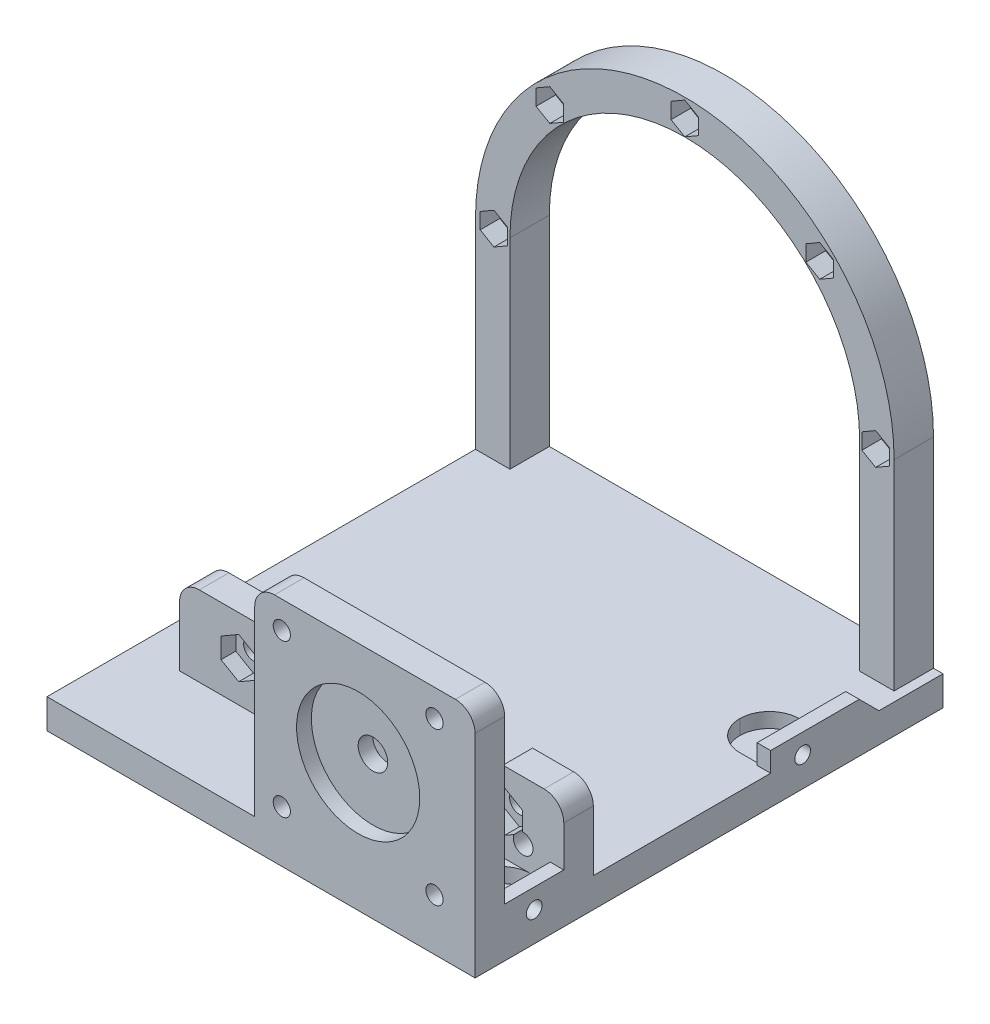
SolidWorks part; units mm, degrees
ref_plane "Front Plane" through (0, 0, 0) normal (0, 0, 1) x (1, 0, 0)
ref_plane "Top Plane" through (0, 0, 0) normal (0, 1, 0) x (1, 0, 0)
ref_plane "Right Plane" through (0, 0, 0) normal (1, 0, 0) x (0, 0, -1)
sketch "Sketch1" plane through (0, 0, 0) normal (0, 0, 1) x (1, 0, 0)
  circle A0 centre (0, 0) radius 3.5
  circle A1 centre (-13.7, 0) radius 2.25
  circle A2 centre (13.7, 0) radius 2.25
  circle A3 centre (0, 0) radius 18.5
  dimension "D3" = 4.5
  dimension "D4" = 7
  dimension "D5" = 37
  dimension "D1" = 13.7
  dimension "D2" = 13.7
extrude "Boss-Extrude1" add sketch "Sketch1" along normal blind 6
sketch "Sketch3" plane through (0, 0, 6) normal (0, 0, 1) x (1, 0, 0)
  line L0 (-18.5, 0) -> (-18.5, -46.68)
  line L1 (18.5, 0) -> (18.5, -46.68)
  line L2 (18.5, -46.68) -> (-18.5, -46.68)
  line L3 (15.5, 0) -> (15.5, -43.68)
  line L4 (15.5, -43.68) -> (-15.5, -43.68)
  line L5 (-15.5, 0) -> (-15.5, -43.68)
  line L6 (-15.5, -43.68) -> (0, -18.5) construction
  line L7 (0, -18.5) -> (15.5, -43.68) construction
  line L8 (-15.5, -40.8186) -> (-1.7125, -18.4206)
  line L9 (0, 0) -> (0, -18.5) construction
  line L10 (0, -18.5) -> (0, -43.68) construction
  line L11 (-13.7386, -43.68) -> (0, -21.3614)
  line L12 (15.5, -40.8186) -> (1.7125, -18.4206)
  line L13 (13.7386, -43.68) -> (0, -21.3614)
  line L14 (-15.5, -10.0995) -> (-18.5, 0)
  line L15 (18.5, 0) -> (15.5, -10.0995)
  line L16 (-3, -20.5121) -> (-3, -18.2551)
  line L17 (3, -20.5121) -> (3, -18.2551)
  circle A0 centre (0, 0) radius 18.5 construction
  circle A1 centre (0, 0) radius 18.5
  circle M4 centre (0, 0) radius 18.5
  dimension "D1" = 46.68
  dimension "D3" = 1.5
  dimension "D4" = 1.5
  dimension "D5" = 3
  dimension "D2" = 3
extrude "Boss-Extrude2" add sketch "Sketch3" against normal blind 6 contours L5 L0 L2 L1 L3 L4 M4 | L13 L4 L3 L12 L8 L5 L11 M4 | L12 L17 M4 | L16 L8 M4
sketch "Sketch4" plane through (0, 0, 0) normal (0, 0, 1) x (1, 0, 0)
  line L0 (-33.57, -46.68) -> (-33.57, -40.68)
  line L1 (-18.5, -46.68) -> (44.43, -46.68)
  line L7 (-33.57, -46.68) -> (-18.5, -46.68)
  line L8 (-33.57, -40.68) -> (44.43, -40.68)
  line L9 (44.43, -40.68) -> (44.43, -46.68)
  dimension "D1" = 44.43
  dimension "D2" = 78
  dimension "D3" = 6
extrude "Boss-Extrude3" add sketch "Sketch4" along normal blind 85
ref_plane "Plane1" through (0, 0, 67) normal (0, 0, -1) x (-1, 0, 0)
sketch "Sketch6" plane through (0, 0, 67) normal (0, 0, -1) x (-1, 0, 0)
  line L1 (-44.43, -40.68) -> (33.57, -40.68) construction
  line L2 (-44.43, -46.68) -> (33.57, -46.68) construction
  line L7 (-44.43, -43.68) -> (33.57, -43.68)
  line L8 (-44.43, -43.68) -> (-44.43, -24.43)
  line L9 (-44.43, -24.43) -> (33.57, -24.43)
  line L10 (33.57, -43.68) -> (33.57, -24.43)
  line L11 (-44.43, -46.68) -> (-44.43, -40.68) construction
  circle A0 centre (-32.43, -32.43) radius 2
  circle A1 centre (21.57, -32.43) radius 2
  circle A2 centre (-20.68, -20.68) radius 12
  circle A3 centre (-36.18, -36.18) radius 2
  circle A4 centre (-5.18, -36.18) radius 2
  dimension "D2" = 4
  dimension "D3" = 4
  dimension "D10" = 24
  dimension "D16" = 4
  dimension "D4" = 12
  dimension "D5" = 66
  dimension "D6" = 12
  dimension "D7" = 8
  dimension "D8" = 23.75
  dimension "D9" = 3.75
  dimension "D11" = 3
  dimension "D12" = 11.25
  dimension "D13" = 4.5
  dimension "D14" = 8.25
  dimension "D15" = 31
extrude "Boss-Extrude5" add sketch "Sketch6" along normal blind 6 contours A2 L9 L8 L7 L10 A1 A0
sketch "Sketch5" plane through (0, 0, 85) normal (0, 0, 1) x (1, 0, 0)
  line L0 (44.43, -46.68) -> (44.43, -40.68) construction
  line L5 (44.43, -46.68) -> (-33.57, -46.68) construction
  line L8 (20.68, -20.68) -> (20.68, -5.18) construction
  line L9 (20.68, -20.68) -> (36.18, -20.68) construction
  line L10 (41.68, -43.68) -> (41.68, 0.32)
  line L11 (-0.32, -43.68) -> (-0.32, 0.32)
  line L12 (-0.32, 0.32) -> (41.68, 0.32)
  circle A0 centre (20.68, -20.68) radius 3
  circle A1 centre (36.18, -5.18) radius 1.75
  circle A2 centre (36.18, -36.18) radius 1.75
  circle A3 centre (5.18, -36.18) radius 1.75
  circle A4 centre (5.18, -5.18) radius 1.75
  dimension "D3" = 6
  dimension "D6" = 3.5
  dimension "D2" = 23
  dimension "D4" = 15.5
  dimension "D5" = 15.5
  dimension "D7" = 21
  dimension "D8" = 21
  dimension "D9" = 2.75
  dimension "D10" = 3
extrude "Boss-Extrude4" add sketch "Sketch5" against normal blind 6
sketch "Sketch8" plane through (44.43, 0, 0) normal (1, 0, 0) x (0, 0, -1)
  line L0 (0, -46.68) -> (0, -40.68) construction
  line L1 (0, -43.68) -> (-25, -43.68)
  line L2 (0, -43.68) -> (0, -36.68)
  line L3 (0, -36.68) -> (-25, -36.68)
  line L4 (-25, -43.68) -> (-25, -36.68)
  line L7 (-79, -43.68) -> (-61, -43.68)
  line L8 (-79, -43.68) -> (-79, -36.68)
  line L9 (-79, -36.68) -> (-61, -36.68)
  line L10 (-61, -43.68) -> (-61, -36.68)
  line L11 (-79, -36.68) -> (-85, -36.68)
  line L12 (-79, -36.68) -> (-79, -43.68)
  line L13 (-79, -43.68) -> (-85, -43.68)
  line L14 (-85, -36.68) -> (-85, -43.68)
  line L15 (-85, -46.68) -> (0, -46.68) construction
  line L16 (-85, -46.68) -> (-85, -40.68) construction
  line L17 (-79, -40.68) -> (-79, 0.32) construction
  line L18 (-85, 0.32) -> (-79, 0.32)
  line L19 (-85, 0.32) -> (-85, -36.68)
  line L20 (-85, -36.68) -> (-79, -36.68)
  line L21 (-79, 0.32) -> (-79, -36.68)
  dimension "D6" = 7
  dimension "D7" = 7
  dimension "D8" = 18
  dimension "D9" = 3
extrude "Boss-Extrude7" add sketch "Sketch8" against normal blind 2.75
chamfer "Chamfer2" distance 7 angle 45 1 edges at (43.055, -36.68, 0)
sketch "Sketch9" plane through (44.43, 0, 0) normal (1, 0, 0) x (0, 0, -1)
  line L2 (-85, -46.68) -> (-85, 0.32) construction
  line L3 (-61, -40.68) -> (-25, -40.68) construction
  circle A2 centre (-73, -40.68) radius 1.6
  circle A3 centre (-18.5, -40.68) radius 1.6
  dimension "D2" = 3.2
  dimension "D3" = 3.2
  dimension "D1" = 12
  dimension "D4" = 54.5
extrude "Cut-Extrude2" cut sketch "Sketch9" against normal blind 10
sketch "Sketch10" plane through (0, -40.68, 0) normal (0, 1, 0) x (1, 0, 0)
  line L0 (41.68, -3) -> (41.68, -16.9) construction
  line L1 (41.68, -12.5) -> (31.68, -12.5)
  line L2 (41.68, -12.5) -> (41.68, -24.5)
  line L3 (41.68, -24.5) -> (31.68, -24.5)
  line L4 (31.68, -12.5) -> (31.68, -24.5)
  line L5 (34.43, -18.5) -> (44.43, -18.5) construction
  line L7 (44.43, -7) -> (44.43, -25) construction
  line L8 (34.43, -73) -> (44.43, -73) construction
  line L9 (34.43, -74.6) -> (34.43, -71.4) construction
  line L10 (44.43, -67) -> (44.43, -79) construction
  line L11 (34.43, -16.9) -> (34.43, -20.1) construction
  line L12 (41.6964, -67) -> (31.6964, -67)
  line L13 (41.6964, -67) -> (41.6964, -79)
  line L14 (41.6964, -79) -> (31.6964, -79)
  line L15 (31.6964, -67) -> (31.6964, -79)
  line L16 (55, -67) -> (-55, -67) construction
  dimension "D1" = 6
  dimension "D2" = 6
  dimension "D3" = 10
  dimension "D4" = 6
  dimension "D5" = 10
extrude "Cut-Extrude3" cut sketch "Sketch10" against normal blind 3
fillet "Fillet1" radius 6 4 edges at (31.6964, -42.18, 67) (31.6964, -42.18, 79) (31.68, -42.18, 24.5) (31.68, -42.18, 12.5)
sketch "Sketch13" plane through (0, 0, 0) normal (0, 0, -1) x (-1, 0, 0)
  line L0 (-18.5, 0) -> (-18.5, -40.68)
  line L1 (-18.5, -40.68) -> (-11.8919, -40.68)
  line L2 (-11.8919, -40.68) -> (0, -21.3614)
  line L3 (0, -21.3614) -> (11.8919, -40.68)
  line L4 (11.8919, -40.68) -> (18.5, -40.68)
  line L5 (18.5, -40.68) -> (18.5, 0)
  line L6 (15.5, -10.0995) -> (15.5, -40.68)
  line L7 (15.4147, -40.68) -> (3, -20.5121)
  line L8 (3, -20.5121) -> (3, -18.2551)
  line L9 (-3, -18.2551) -> (-3, -20.5121)
  line L10 (-3, -20.5121) -> (-15.4147, -40.68)
  line L11 (-15.5, -40.68) -> (-15.5, -10.0995)
  circle A0 centre (0, 0) radius 18.5
  line M2 (15.5, -10.0995) -> (15.5, -40.68)
  line M4 (15.4147, -40.68) -> (3, -20.5121)
  line M5 (3, -20.5121) -> (3, -18.2551)
  arc M6 (3, -18.2551) -> (15.5, -10.0995) centre (0, 0) ccw
  line M7 (0, -21.3614) -> (11.8919, -40.68)
  line M9 (-11.8919, -40.68) -> (0, -21.3614)
  line M10 (-3, -20.5121) -> (-15.4147, -40.68)
  line M12 (-15.5, -40.68) -> (-15.5, -10.0995)
  arc M13 (-15.5, -10.0995) -> (-3, -18.2551) centre (0, 0) ccw
  line M14 (-3, -18.2551) -> (-3, -20.5121)
  line M15 (-18.5, 0) -> (-18.5, -43.68)
  line M21 (18.5, -40.68) -> (18.5, 0)
  arc M22 (18.5, 0) -> (-18.5, 0) centre (0, 0) ccw
  circle M23 centre (-13.7, 0) radius 2.25
  circle M24 centre (13.7, 0) radius 2.25
  circle M25 centre (0, 0) radius 3.5
extrude "Cut-Extrude4" cut sketch "Sketch13" against normal blind 10 contours A0 L1 L4 M14 M10 M9 M7 M4 M5 | A0 L1 M15 M12 | A0 L4 M2 M21 | A0 M22 M13 M6 M23 M25 M24
fillet "Fillet2" radius 4 6 edges at (44.43, -24.43, 64) (-33.57, -24.43, 64) (-0.32, 0.32, 82) (44.43, 0.32, 82) (-33.57, -43.68, 0) (-33.57, -43.68, 85)
sketch "Sketch15" plane through (0, -40.68, 0) normal (0, 1, 0) x (1, 0, 0)
  line L0 (18.5, 0) -> (-29.57, 0) construction
  line L1 (-33.57, -4) -> (44.43, -4)
  line L2 (-33.57, -4) -> (-33.57, 10)
  line L3 (-33.57, 10) -> (44.43, 10)
  line L4 (44.43, -4) -> (44.43, 10)
  dimension "D1" = 10
extrude "Boss-Extrude9" add sketch "Sketch15" against normal up to surface (6 mm away) up to face at (-6.5128, -46.68, 42.5)
sketch "Sketch17" plane through (0, -40.68, 0) normal (0, 1, 0) x (1, 0, 0)
  line L0 (0, -61) -> (0, 10) construction
  line L2 (44.43, 10) -> (-33.57, 10) construction
  line L3 (-33.57, -61) -> (44.43, -61) construction
  line L4 (42.5, 10) -> (-42.5, 10)
  line L5 (42.5, 10) -> (42.5, 2)
  line L6 (42.5, 2) -> (-42.5, 2)
  line L7 (-42.5, 10) -> (-42.5, 2)
  dimension "D1" = 85
  dimension "D2" = 42.5
  dimension "D3" = 8
extrude "Boss-Extrude10" add sketch "Sketch17" along normal blind 86
sketch "Sketch18" plane through (0, 0, -2) normal (0, 0, -1) x (-1, 0, 0)
  line L0 (0, 45.32) -> (0, -46.68) construction
  line L1 (-42.5, 45.32) -> (42.5, 45.32) construction
  line L2 (33.57, -46.68) -> (-44.43, -46.68) construction
  line L3 (42.5, 2.32) -> (-42.5, 2.32) construction
  line L5 (-42.5, 45.32) -> (-42.5, -40.68) construction
  line L6 (35.5, 0) -> (35.5, -40.68)
  line L7 (-42.5, 44.32) -> (42.5, 44.32)
  line L8 (-42.5, 44.32) -> (-42.5, -40.68)
  line L9 (-42.5, -40.68) -> (42.5, -40.68)
  line L10 (42.5, 44.32) -> (42.5, -40.68)
  line L11 (42.5, 2.32) -> (42.5, -40.68)
  line L12 (-35.5, 0) -> (-35.5, -40.68)
  line L14 (42.5, 44.32) -> (-42.5, 44.32)
  line L15 (42.5, 44.32) -> (42.5, 45.32)
  line L16 (42.5, 45.32) -> (-42.5, 45.32)
  line L17 (-42.5, 44.32) -> (-42.5, 45.32)
  circle A0 centre (0, 0) radius 42.5
  circle A1 centre (0, 0) radius 35.5
  line M24 (42.5, -40.68) -> (33.57, -40.68)
  line M25 (33.57, -40.68) -> (-42.5, -40.68)
  line M26 (-42.5, -40.68) -> (-42.5, 45.32)
  line M27 (-42.5, 45.32) -> (42.5, 45.32)
  line M28 (42.5, 45.32) -> (42.5, -40.68)
  dimension "D1" = 85
  dimension "D2" = 71
  dimension "D3" = 40.68
extrude "Cut-Extrude8" cut sketch "Sketch18" along normal blind 85 contours L10 A0 L8 L7 M28 | L7 M26 M27 M28 | A1 | L12 A1 L6 A0 L9 | A0 L6 M25 M24 | L12 A0 M25
sketch "Sketch19" plane through (0, -46.68, 0) normal (0, -1, 0) x (1, 0, 0)
  line L0 (-42.5, -10) -> (-42.5, -2) construction
  line L1 (-33.57, -10) -> (-42.5, -10)
  line L2 (-33.57, -10) -> (-18.1047, 85)
  line L3 (-18.1047, 85) -> (-42.5, 85)
  line L4 (-42.5, -10) -> (-42.5, 85)
extrude "Boss-Extrude11" add sketch "Sketch19" against normal up to surface (6 mm away) up to face at (0.8032, -40.68, 77.1036)
sketch "Sketch21" plane through (0, 0, -2) normal (0, 0, 1) x (1, 0, 0)
  circle A0 centre (0, 0) radius 38.75
  circle A1 centre (-38.75, 0) radius 1.7
  circle A2 centre (-27.4004, 27.4004) radius 1.7
  circle A3 centre (0, 38.75) radius 1.7
  circle A4 centre (27.4004, 27.4004) radius 1.7
  circle A5 centre (38.75, 0) radius 1.7
  dimension "D1" = 77.5
  dimension "D2" = 3.4
  dimension "D3" = 5
extrude "Cut-Extrude9" cut sketch "Sketch21" against normal blind 85 contours A0 A1 | A0 A1 | A0 A2 | A0 A2 | A0 A3 | A0 A3 | A0 A4 | A0 A4 | A0 A5 | A0 A5
sketch "Sketch22" plane through (0, 0, -2) normal (0, 0, 1) x (1, 0, 0)
  line L1 (38.75, 3.2332) -> (35.95, 1.6166)
  line L2 (35.95, 1.6166) -> (35.95, -1.6166)
  line L3 (35.95, -1.6166) -> (38.75, -3.2332)
  line L4 (38.75, -3.2332) -> (41.55, -1.6166)
  line L5 (41.55, -1.6166) -> (41.55, 1.6166)
  line L6 (41.55, 1.6166) -> (38.75, 3.2332)
  line L7 (27.4004, 30.6335) -> (24.6004, 29.017)
  line L8 (24.6004, 29.017) -> (24.6004, 25.7838)
  line L9 (24.6004, 25.7838) -> (27.4004, 24.1672)
  line L10 (27.4004, 24.1672) -> (30.2004, 25.7838)
  line L11 (30.2004, 25.7838) -> (30.2004, 29.017)
  line L12 (30.2004, 29.017) -> (27.4004, 30.6335)
  line L13 (0, 41.9832) -> (-2.8, 40.3666)
  line L14 (-2.8, 40.3666) -> (-2.8, 37.1334)
  line L15 (-2.8, 37.1334) -> (0, 35.5168)
  line L16 (0, 35.5168) -> (2.8, 37.1334)
  line L17 (2.8, 37.1334) -> (2.8, 40.3666)
  line L18 (2.8, 40.3666) -> (0, 41.9832)
  line L19 (-27.4004, 30.6335) -> (-30.2004, 29.017)
  line L20 (-30.2004, 29.017) -> (-30.2004, 25.7838)
  line L21 (-30.2004, 25.7838) -> (-27.4004, 24.1672)
  line L22 (-27.4004, 24.1672) -> (-24.6004, 25.7838)
  line L23 (-24.6004, 25.7838) -> (-24.6004, 29.017)
  line L24 (-24.6004, 29.017) -> (-27.4004, 30.6335)
  line L25 (-38.75, 3.2332) -> (-41.55, 1.6166)
  line L26 (-41.55, 1.6166) -> (-41.55, -1.6166)
  line L27 (-41.55, -1.6166) -> (-38.75, -3.2332)
  line L28 (-38.75, -3.2332) -> (-35.95, -1.6166)
  line L29 (-35.95, -1.6166) -> (-35.95, 1.6166)
  line L30 (-35.95, 1.6166) -> (-38.75, 3.2332)
  circle A0 centre (38.75, 0) radius 2.8 construction
  circle A1 centre (27.4004, 27.4004) radius 2.8 construction
  circle A2 centre (0, 38.75) radius 2.8 construction
  circle A3 centre (-27.4004, 27.4004) radius 2.8 construction
  circle A4 centre (-38.75, 0) radius 2.8 construction
  dimension "D1" = 5.6
  dimension "D2" = 5.6
  dimension "D3" = 5.6
  dimension "D4" = 5.6
  dimension "D5" = 5.6
extrude "Cut-Extrude10" cut sketch "Sketch22" against normal blind 4
sketch "Sketch23" plane through (0, 0, 67) normal (0, 0, 1) x (1, 0, 0)
  line L1 (-21.57, -28.2731) -> (-25.17, -30.3515)
  line L2 (-25.17, -30.3515) -> (-25.17, -34.5085)
  line L3 (-25.17, -34.5085) -> (-21.57, -36.5869)
  line L4 (-21.57, -36.5869) -> (-17.97, -34.5085)
  line L5 (-17.97, -34.5085) -> (-17.97, -30.3515)
  line L6 (-17.97, -30.3515) -> (-21.57, -28.2731)
  line L7 (32.43, -28.2731) -> (28.83, -30.3515)
  line L8 (28.83, -30.3515) -> (28.83, -34.5085)
  line L9 (28.83, -34.5085) -> (32.43, -36.5869)
  line L10 (32.43, -36.5869) -> (36.03, -34.5085)
  line L11 (36.03, -34.5085) -> (36.03, -30.3515)
  line L12 (36.03, -30.3515) -> (32.43, -28.2731)
  circle A0 centre (-21.57, -32.43) radius 3.6 construction
  circle A1 centre (32.43, -32.43) radius 3.6 construction
  dimension "D1" = 7.2
  dimension "D2" = 7.2
extrude "Cut-Extrude11" cut sketch "Sketch23" against normal blind 3
sketch "Sketch24" plane through (0, 0, 85) normal (0, 0, 1) x (1, 0, 0)
  circle A0 centre (20.68, -20.68) radius 12.5
  dimension "D1" = 25
extrude "Cut-Extrude12" cut sketch "Sketch24" against normal blind 3
